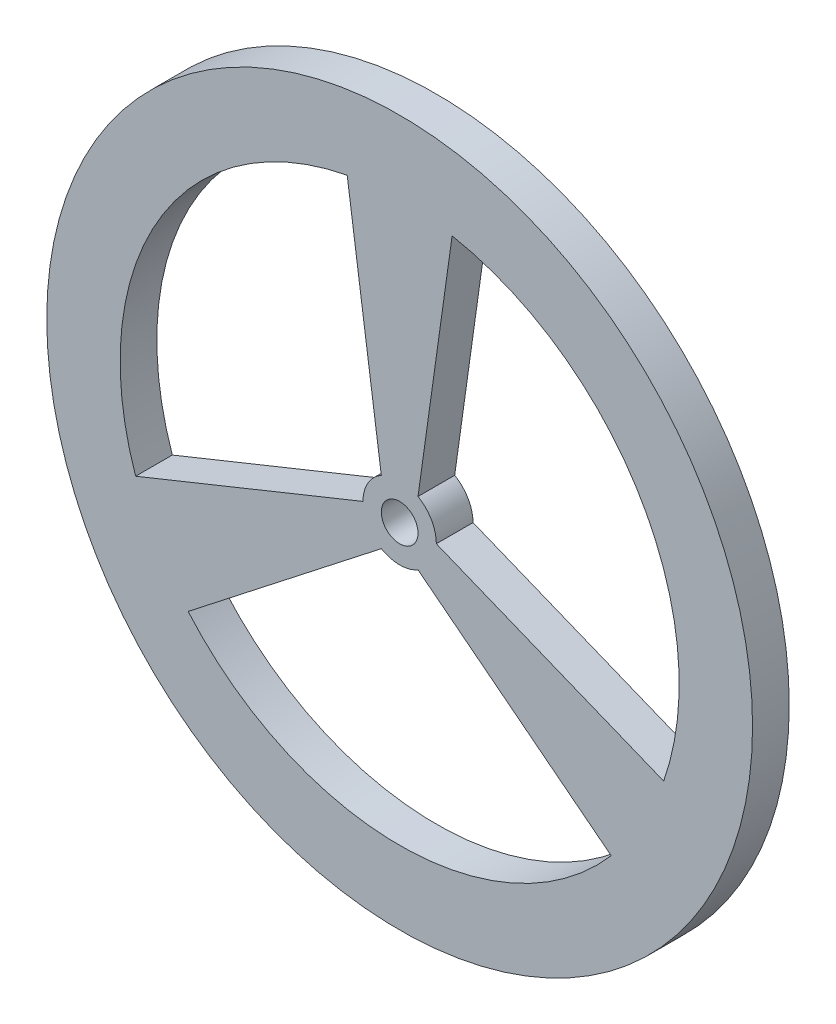
SolidWorks part; units mm, degrees
ref_plane "Front Plane" through (0, 0, 0) normal (0, 0, 1) x (1, 0, 0)
ref_plane "Top Plane" through (0, 0, 0) normal (0, 1, 0) x (1, 0, 0)
ref_plane "Right Plane" through (0, 0, 0) normal (1, 0, 0) x (0, 0, -1)
sketch "Sketch1" plane through (0, 0, 0) normal (0, 0, 1) x (1, 0, 0)
  line L0 (-2.5, 4.3301) -> (-7.1509, 37.4229)
  line L1 (2.5, 4.3301) -> (7.1509, 37.4229)
  line L2 (0, 85.6753) -> (0, 40.2735) construction
  line L3 (5, 0) -> (35.9846, -12.5186)
  line L4 (2.5, -4.3301) -> (28.8338, -24.9043)
  line L5 (-2.5, -4.3301) -> (-28.8338, -24.9043)
  line L6 (-5, 0) -> (-35.9846, -12.5186)
  circle A0 centre (0, 0) radius 48.1
  circle A1 centre (0, 0) radius 38.1
  circle A2 centre (0, 0) radius 5
  circle A3 centre (0, 0) radius 5
  circle A4 centre (0, 0) radius 5
  circle A5 centre (0, 0) radius 2.5
  point P23 (0, 0)
  dimension "D4" = 76.2
  dimension "D5" = 10
  dimension "D6" = 5
  dimension "D7" = 10
  dimension "D1" = 8
  dimension "D2" = 2.5
  dimension "D3" = 3
extrude "Boss-Extrude1" add sketch "Sketch1" along normal blind 5 contours A1 L2 A2 L1 | L2 A1 L0 A4 | L2 A0 A1 | A2 L4 A1 L3 | A2 L6 A1 L5 | A0 L2 A1 | A2 L2 A5 A4 | L2 A4 A2 A5 region at (0, 23.95, 0) region at (0, 4.8586, 0) region at (-20.7413, -11.975, 0) region at (20.7413, -11.975, 0) region at (-33.0498, -33.0498, 0)
ref_axis "Axis1" through (0, 0, 5) along (0, 0, -1)
